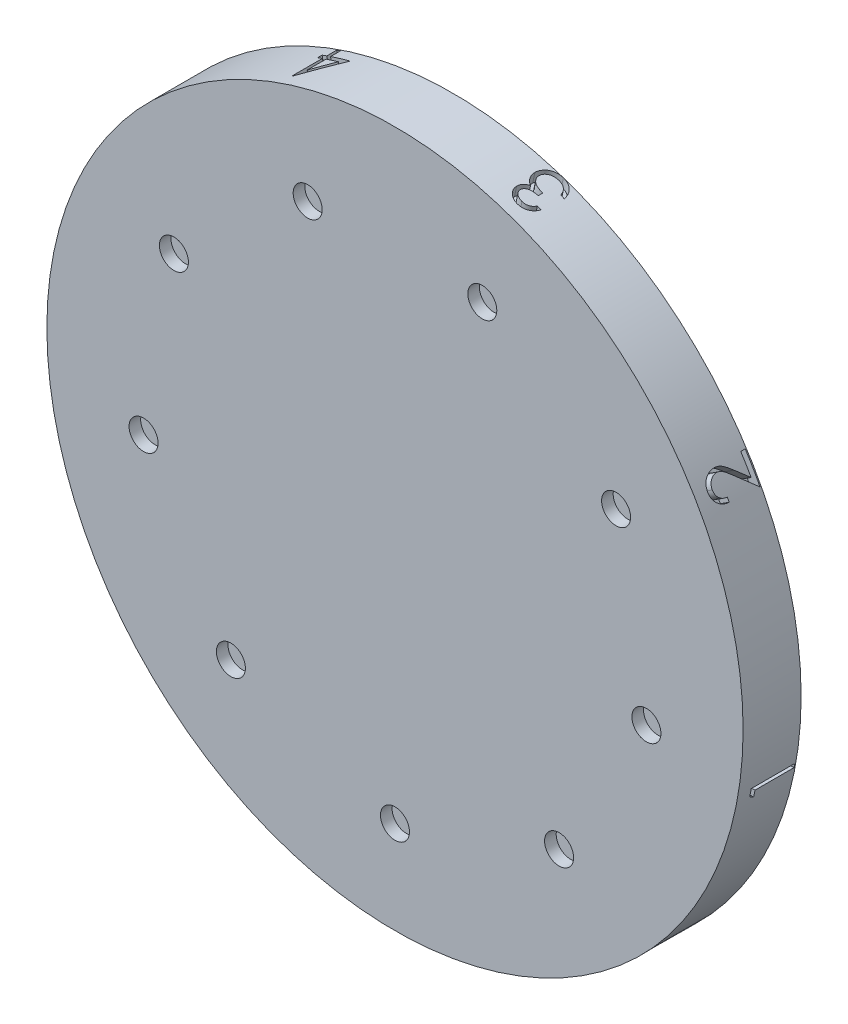
SolidWorks part; units mm, degrees
ref_plane "Front Plane" through (0, 0, 0) normal (0, 0, 1) x (1, 0, 0)
ref_plane "Top Plane" through (0, 0, 0) normal (0, 1, 0) x (1, 0, 0)
ref_plane "Right Plane" through (0, 0, 0) normal (1, 0, 0) x (0, 0, -1)
sketch "Sketch1" plane through (0, 0, 0) normal (0, 0, 1) x (1, 0, 0)
  circle A0 centre (0, 0) radius 76.2
  dimension "D1" = 152.4
extrude "Boss-Extrude1" add sketch "Sketch1" along normal blind 12.7
sketch "Sketch2" plane through (0, 0, 12.7) normal (0, 0, 1) x (1, 0, 0)
  line L0 (-76.2, 0) -> (76.2, 0) construction
  circle A0 centre (0, 0) radius 76.2 construction
  circle A10 centre (0, -55.88) radius 3.175
  circle A11 centre (-35.919, -42.8066) radius 3.175
  circle A12 centre (-55.0311, -9.7035) radius 3.175
  circle A13 centre (-48.3935, 27.94) radius 3.175
  circle A14 centre (-19.1121, 52.51) radius 3.175
  circle A15 centre (19.1121, 52.51) radius 3.175
  circle A16 centre (48.3935, 27.94) radius 3.175
  circle A17 centre (55.0311, -9.7035) radius 3.175
  circle A18 centre (35.919, -42.8066) radius 3.175
  dimension "D1" = 19.1121
  dimension "D2" = 35.919
  dimension "D5" = 6.35
  dimension "D3" = 27.94
  dimension "D7" = 9
extrude "Cut-Extrude2" cut sketch "Sketch2" against normal blind 2.54
sketch "Sketch4" plane through (0, 0, 0) normal (0, 0, -1) x (-1, 0, 0)
  circle A0 centre (0, 0) radius 6.35
  circle A1 centre (0, 0) radius 76.2 construction
  dimension "D1" = 12.7
extrude "Cut-Extrude4" cut sketch "Sketch4" against normal blind 5.08
ref_plane "Plane1" through (76.2, 0, 0) normal (1, 0, 0) x (0, 0, -1)
sketch "Sketch5" plane through (76.2, 0, 0) normal (1, 0, 0) x (0, 0, -1)
  line L2 (-0.254, -32.003) -> (-0.254, 6.097) construction
  text T0 "    1\r\n" font "Century Gothic" height in points 36
  dimension "D1" = 38.1
  dimension "D2" = 32.004
  dimension "D3" = 0.254
  dimension "D4" = 7.8697
  dimension "D5" = 8.351
extrude "Cut-Extrude5" cut sketch "Sketch5" against normal blind 2.54
sketch3d "3DSketch7"
  line L0 (46.0076, 25.8453, 12.7) -> (51.288, 29.2448, 12.7)
  circle A1 centre (48.3935, 27.94, 12.7) radius 3.175 construction
  point P4 (48.3935, 27.94, 15.875)
ref_plane "Plane2" through (64.0703, 41.2485, 0) normal (0.8408, 0.5413, 0) x (0.5413, -0.8408, 0)
sketch "Sketch9" plane through (64.0703, 41.2485, 0) normal (0.8408, 0.5413, 0) x (0.5413, -0.8408, 0)
  line L0 (21.7538, -0.254) -> (-16.3462, -0.254) construction
  line L1 (76.2, 0) -> (-76.2, 0) construction
  text T0 "    2" font "Century Gothic" height in points 36
  dimension "D1" = 0.254
  dimension "D2" = 38.1
  dimension "D3" = 19.05
extrude "Cut-Extrude6" cut sketch "Sketch9" against normal blind 2.54
sketch "Sketch10" plane through (0, 0, 10.16) normal (0, 0, 1) x (1, 0, 0)
  line L0 (30.1125, 61.2861) -> (27.2717, 47.893)
  line L1 (-21.5026, 63.1239) -> (-18.2744, 49.7308)
  line L2 (-46.2354, 26.2801) -> (-56.0083, 32.3659)
  line L4 (-33.733, -40.3165) -> (-37.6367, -45.1341)
  line L5 (0, -53.2566) -> (0, -64.7355)
  line L6 (34.345, -39.9112) -> (37.8345, -45.1341)
  line L7 (-51.8561, -8.6717) -> (-72.1566, -11.3928)
  circle A0 centre (19.1121, 52.51) radius 3.175 construction
  dimension "D1" = 8.1596
  dimension "D2" = 11.0004
  dimension "D3" = 15.2329
  dimension "D4" = 18.7224
  dimension "D5" = 19.1121
  dimension "D6" = 37.3865
  dimension "D7" = 40.6147
  dimension "D8" = 52.8451
  dimension "D9" = 56.7487
  dimension "D10" = 65.3474
  dimension "D11" = 70.9681
  dimension "D12" = 75.1204
  dimension "D13" = 91.2687
  dimension "D14" = 8.7761
  dimension "D15" = 10.6139
  dimension "D16" = 2.7792
  dimension "D17" = 4.617
  dimension "D18" = 20.1441
  dimension "D19" = 26.2299
  dimension "D20" = 61.1817
  dimension "D21" = 63.9028
  dimension "D22" = 92.4212
  dimension "D23" = 92.8265
  dimension "D24" = 97.6441
  dimension "D25" = 105.7666
  dimension "D26" = 117.2455
ref_plane "Plane3" through (15.8107, 74.5417, 0) normal (0.2075, 0.9782, 0) x (0.9782, -0.2075, 0)
sketch "Sketch11" plane through (15.8107, 74.5417, 0) normal (0.2075, 0.9782, 0) x (0.9782, -0.2075, 0)
  line L0 (26.8508, -0.254) -> (-11.2492, -0.254) construction
  line L1 (76.2, 0) -> (-76.2, 0) construction
  text T0 "    3" font "Century Gothic" height in points 36
  dimension "D1" = 38.1
  dimension "D2" = 0.254
  dimension "D3" = 19.05
extrude "Cut-Extrude7" cut sketch "Sketch11" against normal blind 2.54
ref_plane "Plane4" through (-17.8552, 74.0786, 0) normal (-0.2343, 0.9722, 0) x (0.9722, 0.2343, 0)
sketch "Sketch12" plane through (-17.8552, 74.0786, 0) normal (-0.2343, 0.9722, 0) x (0.9722, 0.2343, 0)
  line L0 (12.7741, -0.254) -> (-25.3259, -0.254) construction
  line L1 (76.2, 0) -> (-76.2, 0) construction
  text T0 "    4" font "Century Gothic" height in points 36
  dimension "D1" = 0.254
  dimension "D2" = 38.1
  dimension "D3" = 19.05
extrude "Cut-Extrude8" cut sketch "Sketch12" against normal blind 2.54
ref_plane "Plane5" through (-64.6837, 40.2798, 0) normal (-0.8489, 0.5286, 0) x (0, 0, 1)
sketch "Sketch13" plane through (-64.6837, 40.2798, 0) normal (-0.8489, 0.5286, 0) x (0, 0, 1)
  line L0 (0.254, 17.1863) -> (0.254, -20.9137) construction
  line L1 (0, 76.2) -> (0, -76.2) construction
  text T0 "    5" font "Century Gothic" height in points 36
  dimension "D1" = 0.254
  dimension "D2" = 38.1
  dimension "D3" = 19.05
extrude "Cut-Extrude9" cut sketch "Sketch13" against normal blind 2.54
ref_plane "Plane7" through (-75.5246, -10.1233, 0) normal (-0.9911, -0.1329, 0) x (0, 0, 1)
sketch "Sketch14" plane through (-75.5246, -10.1233, 0) normal (-0.9911, -0.1329, 0) x (0, 0, 1)
  line L0 (0.254, 16.7435) -> (0.254, -21.3565) construction
  line L1 (0, 76.2) -> (0, -76.2) construction
  text T0 "     6" font "Century Gothic" height in points 36
  dimension "D1" = 0.254
  dimension "D2" = 38.1
  dimension "D3" = 19.05
extrude "Cut-Extrude10" cut sketch "Sketch14" against normal blind 2.54
ref_plane "Plane8" through (-47.9721, -59.204, 0) normal (-0.6296, -0.777, 0) x (-0.777, 0.6296, 0)
sketch "Sketch15" plane through (-47.9721, -59.204, 0) normal (-0.6296, -0.777, 0) x (-0.777, 0.6296, 0)
  line L0 (20.0083, -0.254) -> (-18.0917, -0.254) construction
  line L1 (76.2, 0) -> (-76.2, 0) construction
  text T0 "     7" font "Century Gothic" height in points 36
  dimension "D1" = 0.254
  dimension "D2" = 38.1
  dimension "D3" = 19.05
extrude "Cut-Extrude11" cut sketch "Sketch15" against normal blind 2.54
ref_plane "Plane9" through (0, -76.2, 0) normal (0, -1, 0) x (-1, 0, 0)
sketch "Sketch16" plane through (0, -76.2, 0) normal (0, -1, 0) x (-1, 0, 0)
  line L0 (19.05, -0.254) -> (-19.05, -0.254) construction
  line L1 (76.2, 0) -> (-76.2, 0) construction
  text T0 "    8" font "Century Gothic" height in points 36
  dimension "D1" = 0.254
  dimension "D2" = 38.1
  dimension "D3" = 19.05
extrude "Cut-Extrude12" cut sketch "Sketch16" against normal blind 2.54
ref_plane "Plane10" through (42.3318, -63.3598, 0) normal (0.5555, -0.8315, 0) x (-0.8315, -0.5555, 0)
sketch "Sketch17" plane through (42.3318, -63.3598, 0) normal (0.5555, -0.8315, 0) x (-0.8315, -0.5555, 0)
  line L0 (12.9642, -0.254) -> (-25.1358, -0.254) construction
  line L1 (76.2, 0) -> (-76.2, 0) construction
  text T0 "     9" font "Century Gothic" height in points 36
  dimension "D1" = 38.1
  dimension "D2" = 0.254
  dimension "D3" = 19.05
extrude "Cut-Extrude13" cut sketch "Sketch17" against normal blind 2.54
